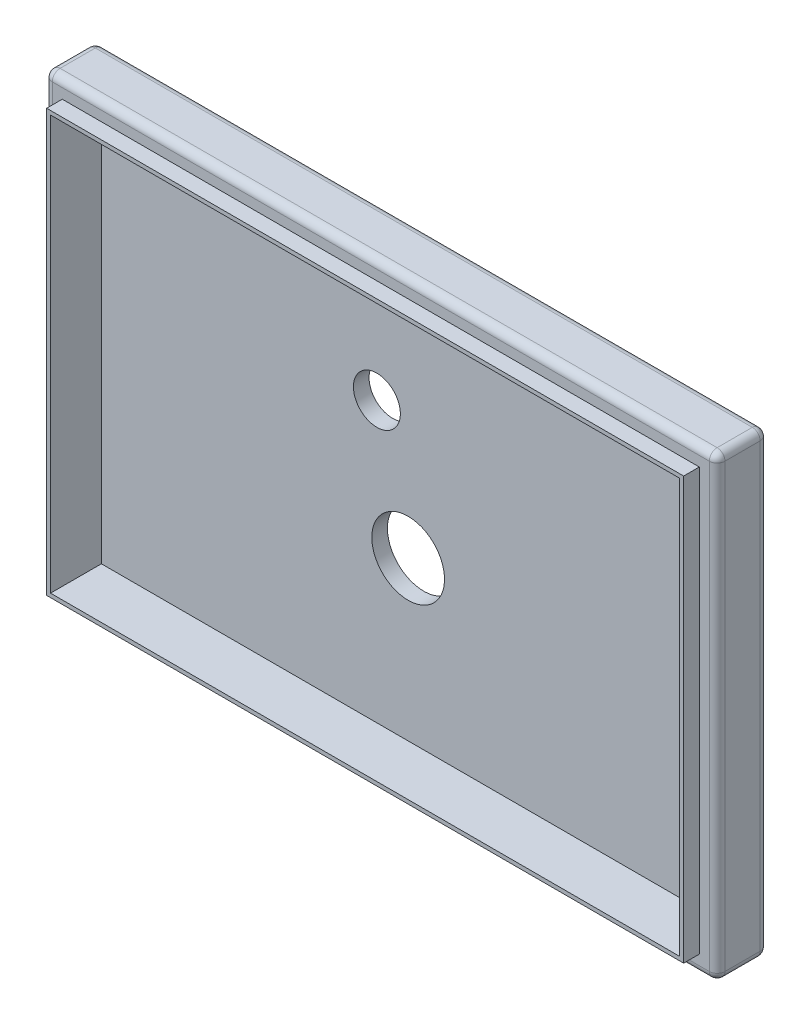
SolidWorks part; units mm, degrees
ref_plane "Front Plane" through (0, 0, 0) normal (0, 0, 1) x (1, 0, 0)
ref_plane "Top Plane" through (0, 0, 0) normal (0, 1, 0) x (1, 0, 0)
ref_plane "Right Plane" through (0, 0, 0) normal (1, 0, 0) x (0, 0, -1)
sketch "Sketch1" plane through (0, 0, 0) normal (0, 0, 1) x (1, 0, 0)
  line L1 (0, 3) -> (86, 3)
  line L2 (0, 3) -> (0, -55.5)
  line L3 (0, -55.5) -> (86, -55.5)
  line L4 (86, 3) -> (86, -55.5)
  dimension "D1" = 58.5
  dimension "D2" = 86
extrude "Boss-Extrude1" add sketch "Sketch1" along normal blind 2
sketch "Sketch2" plane through (0, 0, 2) normal (0, 0, 1) x (1, 0, 0)
  line L0 (0, 3) -> (0, -55.5) construction
  line L1 (2.28, 0.72) -> (83.72, 0.72)
  line L2 (2.28, 0.72) -> (2.28, -53.22)
  line L3 (2.28, -53.22) -> (83.72, -53.22)
  line L4 (83.72, 0.72) -> (83.72, -53.22)
  line L5 (86, -55.5) -> (86, 3) construction
  line L6 (0, -55.5) -> (86, -55.5) construction
  line L7 (86, 3) -> (0, 3) construction
  dimension "D1" = 2.28
  dimension "D2" = 2.28
  dimension "D3" = 2.28
  dimension "D4" = 2.28
extrude "Boss-Extrude3" add sketch "Sketch2" along normal blind 6.5 separate body
shell "Shell5" thickness 0.5 removed face at (43, -26.25, 8.5)
sketch "Sketch3" plane through (0, 0, 0) normal (0, 0, -1) x (-1, 0, 0)
  line L0 (0, -55.5) -> (-86, -55.5) construction
  line L1 (-86, -55.5) -> (-86, 3) construction
  line L3 (-86, 3) -> (0, 3) construction
  circle A0 centre (-42, -32.5) radius 4.65
  circle A1 centre (-38, -17) radius 3
  dimension "D1" = 23
  dimension "D3" = 48
  dimension "D4" = 20
  dimension "D2" = 44
extrude "Cut-Extrude1" cut sketch "Sketch3" against normal blind 2
sketch "Sketch7" plane through (0, 0, 2.5) normal (0, 0, 1) x (1, 0, 0)
  line L0 (83.22, 0.22) -> (2.78, 0.22) construction
  line L1 (2.78, 0.22) -> (83.22, 0.22)
  line L2 (2.78, 0.22) -> (2.78, -52.72)
  line L3 (2.78, -52.72) -> (83.22, -52.72)
  line L4 (83.22, 0.22) -> (83.22, -52.72)
  line L5 (83.22, -52.72) -> (83.22, 0.22) construction
  line L6 (2.78, -52.72) -> (83.22, -52.72) construction
  line L7 (2.78, 0.22) -> (2.78, -52.72) construction
  dimension "D1" = 0
  dimension "D2" = 0
  dimension "D3" = 0
  dimension "D4" = 0
extrude "Cut-Extrude2" cut sketch "Sketch7" against normal blind 5.5
sketch "Sketch8" plane through (0, 0, 2) normal (0, 0, 1) x (1, 0, 0)
  line L0 (86, 3) -> (0, 3) construction
  line L1 (86, 3) -> (0, 3)
  line L2 (86, 3) -> (86, 0.72)
  line L3 (86, 0.72) -> (0, 0.72)
  line L4 (0, 3) -> (0, 0.72)
  line L5 (83.72, 0.72) -> (2.28, 0.72) construction
  line L6 (86, -55.5) -> (86, 3) construction
  line L7 (83.72, -53.22) -> (83.72, 0.72) construction
  line L8 (0, 3) -> (0, -55.5) construction
  line L13 (86, 0.72) -> (83.72, 0.72)
  line L14 (86, 0.72) -> (86, -55.5)
  line L15 (86, -55.5) -> (83.72, -55.5)
  line L16 (83.72, 0.72) -> (83.72, -55.5)
  line L17 (0, -55.5) -> (86, -55.5) construction
  line L18 (2.28, -53.22) -> (83.72, -53.22) construction
  line L19 (83.72, -53.22) -> (0, -53.22)
  line L20 (83.72, -53.22) -> (83.72, -55.5)
  line L21 (83.72, -55.5) -> (0, -55.5)
  line L22 (0, -53.22) -> (0, -55.5)
  line L23 (2.28, 0.72) -> (2.28, -53.22) construction
  line L24 (2.28, 0.72) -> (0, 0.72)
  line L25 (2.28, 0.72) -> (2.28, -53.22)
  line L26 (2.28, -53.22) -> (0, -53.22)
  line L27 (0, 0.72) -> (0, -53.22)
  line M6 (0, 3) -> (0, -55.5)
  line M7 (0, -55.5) -> (86, -55.5)
  line M8 (86, -55.5) -> (86, 3)
  line M9 (86, 3) -> (0, 3)
  dimension "D1" = 0
  dimension "D2" = 0
  dimension "D3" = 0
  dimension "D4" = 0
  dimension "D5" = 0
  dimension "D6" = 0
  dimension "D7" = 0
  dimension "D8" = 0
  dimension "D9" = 0
  dimension "D10" = 0
  dimension "D11" = 0
  dimension "D12" = 0
  dimension "D13" = 0
  dimension "D14" = 0
  dimension "D15" = 0
  dimension "D16" = 0
extrude "Boss-Extrude4" add sketch "Sketch8" along normal blind 4.5 contours L3 M8 M9 M6 | L16 L19 M6 M7 | L14 L15 L16 L13 | L25 L26 L27 L24 region at (43, 1.86, 2) region at (41.86, -54.36, 2)
fillet "Fillet1" radius 1 7 edges at (43, 3, 6.5) (0, 3, 3.25) (43, 3, 0) (86, -55.5, 3.25) (86, -26.25, 6.5) (86, 3, 3.25) (86, -26.25, 0)
fillet "Fillet2" radius 1 9 edges at (0.2929, 2.7071, 0.2929) (0.2929, 2.7071, 6.2071) (85.7071, -55.2071, 6.2071) (85.7071, -55.2071, 0.2929) (0, -26.75, 0) (0, -26.75, 6.5) (0, -55.5, 3.25) (42.5, -55.5, 6.5) (42.5, -55.5, 0)
